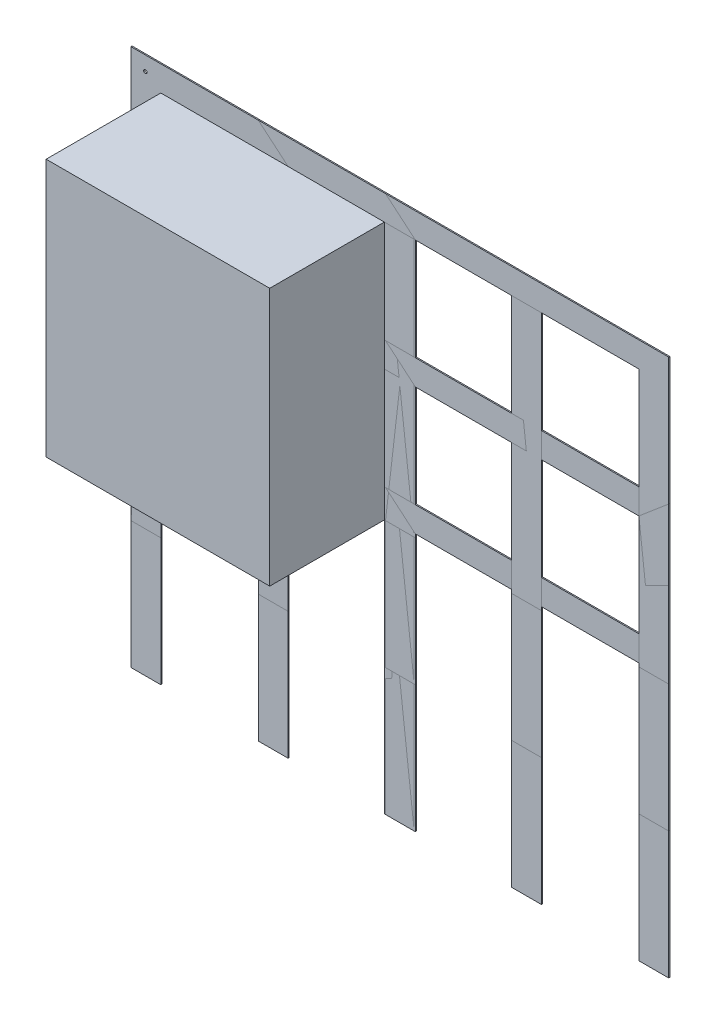
SolidWorks part; units mm, degrees
note: '?' marks a value the reader was unsure of.
ref_plane "Front Plane" through (0, 0, 0) normal (0, 0, 1) x (1, 0, 0)
ref_plane "Top Plane" through (0, 0, 0) normal (0, 1, 0) x (1, 0, 0)
ref_plane "Right Plane" through (0, 0, 0) normal (1, 0, 0) x (0, 0, -1)
ref_plane "Plane1"
sketch "Sketch1" plane through (0, 0, 0) normal (0, 0, 1) x (1, 0, 0)
  line L0 (-195, 203) -> (-195, -247)
  line L1 (-195, -247) -> (195, -247)
  line L2 (195, -247) -> (195, 203)
  line L3 (195, 203) -> (-195, 203)
  dimension "D1" = 390
  dimension "D2" = 450
extrude "Extrusion2" add sketch "Sketch1" along normal blind 200
shell "Shell2" thickness 2
ref_plane "Plane2" through (0, 0, 0) normal (0, 0, 1) x (1, 0, 0)
sketch "Sketch2" plane through (0, 0, 0) normal (0, 0, 1) x (1, 0, 0)
  line L0 (-247, -247) -> (-195, -247)
  line L1 (-195, -247) -> (-195, 203)
  line L2 (-195, 203) -> (195, 203)
  line L3 (195, 203) -> (195, -247)
  line L4 (195, -247) -> (247, -247)
  line L5 (247, -247) -> (247, 247)
  line L6 (247, 247) -> (-247, 247)
  line L7 (-247, 247) -> (-247, -247)
  dimension "D1" = 494
  dimension "D2" = 494
  dimension "D3" = 390
  dimension "D4" = 450
extrude "Extrusion3" add sketch "Sketch2" against normal blind 2
hole_wizard "Hole1" positions "Sketch4" profile "Sketch3" legacy end condition through all
sketch "Sketch4" plane through (0, 0, 0) normal (0, 0, 1) x (1, 0, 0)
  point P1 (-222, 222)
sketch "Sketch3" plane through (-222, 222, 0) normal (1, 0, 0) x (0, -1, 0)
  line L0 (0, 0) -> (0, 2)
  line L1 (0, 2) -> (3, 2)
  line L2 (3, 2) -> (3, 0)
  line L3 (3, 0) -> (0, 0)
  line L4 (0, 110) -> (0, -10) construction
  dimension "Diameter" = 6
  dimension "Depth" = 2
ref_plane "Plane3" through (0, 0, 0) normal (0, -1, 0) x (-1, 0, 0)
ref_plane "Plane4" through (0, 0, 0) normal (0, 0, 1) x (1, 0, 0)
ref_axis "Axis1" through (-80.9, 0, 0) along (1, 0, 0)?
ref_plane "Plane5" through (0, 0, 0) normal (0, 0, -1) x (-1, 0, 0)
ref_plane "Plane6" through (0, 0, 0) normal (-1, 0, 0) x (0, 0, 1)
ref_axis "Axis2" through (0, 50, 0) along (0, -1, 0)?
pattern_linear "Rectangular Pattern1" count 3 spacing 222 along (1, 0, 0) count 3 spacing 222 along (0, -1, 0) of bodies 103
sketch "Sketch5" plane through (0, -245, 0) normal (0, 1, 0) x (-1, 0, 0)
  line L0 (-193, 0) -> (193, 0)
  line L1 (193, 0) -> (193, 198)
  line L2 (193, 198) -> (-193, 198)
  line L3 (-193, 198) -> (-193, 0)
extrude "Extrusion4" cut sketch "Sketch5" against normal up to next (2 mm away)
